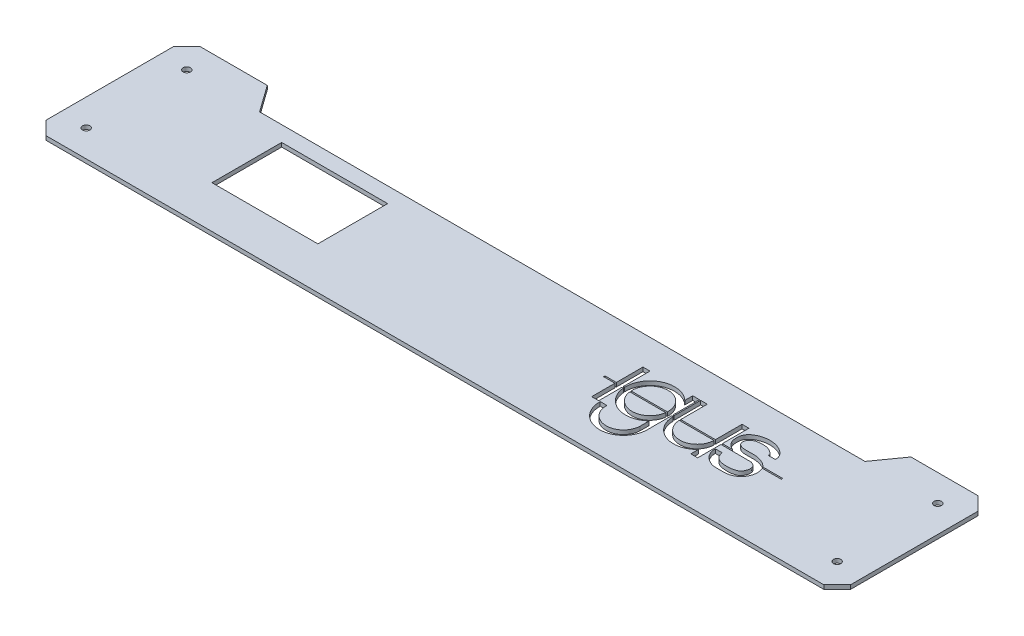
SolidWorks part; units mm, degrees
ref_plane "Front Plane" through (0, 0, 0) normal (0, 0, 1) x (1, 0, 0)
ref_plane "Top Plane" through (0, 0, 0) normal (0, 1, 0) x (1, 0, 0)
ref_plane "Right Plane" through (0, 0, 0) normal (1, 0, 0) x (0, 0, -1)
sketch "Sketch1" plane through (0, 0, 0) normal (0, 1, 0) x (1, 0, 0)
  line L0 (44.6193, 0) -> (44.6193, -115) construction
  line L1 (14.6193, 0) -> (64.6193, 0)
  line L2 (4.6193, -10) -> (4.6193, -105)
  line L3 (14.6193, -115) -> (64.6193, -115)
  line L4 (564.6193, 0) -> (564.6193, -115) construction
  line L6 (4.6193, -10) -> (14.6193, 0)
  line L7 (4.6193, -105) -> (14.6193, -115)
  line L9 (78.8949, -20) -> (530.3437, -20)
  line L10 (78.8949, -20) -> (64.6193, 0)
  line L11 (304.6193, 0) -> (304.6193, -115) construction
  line L12 (530.3437, -20) -> (544.6193, 0)
  line L13 (604.6193, -105) -> (594.6193, -115)
  line L14 (604.6193, -10) -> (594.6193, 0)
  line L16 (594.6193, -115) -> (544.6193, -115)
  line L17 (604.6193, -10) -> (604.6193, -105)
  line L18 (594.6193, 0) -> (544.6193, 0)
  line L19 (64.6193, -115) -> (544.6193, -115)
  circle A0 centre (24.6193, -20) radius 2.75
  circle A1 centre (24.6193, -95) radius 2.75
  circle A2 centre (584.6193, -95) radius 2.75
  circle A3 centre (584.6193, -20) radius 2.75
  point P0 (4.6193, 0)
  point P2 (4.6193, -115)
  point P28 (304.6193, -20)
  point P29 (304.6193, -95)
  point P34 (604.6193, -115)
  point P35 (604.6193, 0)
  dimension "D4" = 5.5
  dimension "D5" = 20
  dimension "D1" = 115
  dimension "D2" = 300
  dimension "D3" = 40
  dimension "D6" = 20
  dimension "D7" = 20
  dimension "D8" = 20
  dimension "D9" = 20
  dimension "D10" = 20
extrude "Boss-Extrude1" add sketch "Sketch1" along normal blind 3
sketch "Sketch2" plane through (0, 3, 0) normal (0, 1, 0) x (1, 0, 0)
  line L0 (393.0027, -80.0768) -> (398.0021, -80.0768)
  line L1 (386.6123, -41.8475) -> (391.8479, -41.8475)
  line L2 (386.6123, -41.8475) -> (386.6123, -61.6873)
  line L3 (386.6123, -80.0768) -> (391.8479, -80.0768)
  line L4 (391.8479, -41.8475) -> (391.8479, -61.6873)
  line L5 (423.7383, -47.7863) -> (423.7383, -41.8475)
  line L6 (466.527, -67.6702) -> (471.6598, -67.6702)
  line L7 (428.7377, -81.1843) -> (428.7377, -41.8475)
  line L8 (428.7377, -41.8475) -> (423.7383, -41.8475)
  line L9 (423.7383, -81.1843) -> (423.7383, -74.2978)
  line L10 (460.5247, -61.6873) -> (460.5247, -41.8475)
  line L11 (460.5247, -80.0768) -> (465.6606, -80.0768)
  line L12 (460.5247, -80.0768) -> (460.5247, -74.3998)
  line L13 (460.5247, -41.8475) -> (465.6606, -41.8475)
  line L14 (465.6606, -80.0768) -> (465.6606, -62.7545)
  line L15 (490.3889, -52.2144) -> (495.6647, -52.2144)
  line L16 (434.5855, -41.8475) -> (429.6272, -41.8475)
  line L17 (434.5855, -41.8475) -> (434.5855, -61.6873)
  line L18 (434.5855, -61.6873) -> (460.5247, -61.6873)
  line L19 (429.6272, -41.8475) -> (429.6272, -61.6873)
  line L20 (386.6123, -62.7545) -> (386.6123, -80.0768)
  line L21 (378.213, -61.6873) -> (386.6123, -61.6873)
  line L22 (378.213, -61.6873) -> (378.213, -62.7545)
  line L23 (378.213, -62.7545) -> (386.6123, -62.7545)
  line L24 (510.6818, -61.6873) -> (510.6818, -62.7545)
  line L25 (391.8479, -61.6873) -> (392.8262, -61.6873)
  line L26 (391.8479, -62.7545) -> (392.8952, -62.7545)
  line L27 (391.8479, -62.7545) -> (391.8479, -80.0768)
  line L28 (397.6051, -61.6873) -> (424.6303, -61.6873)
  line L29 (397.6985, -62.7545) -> (424.5369, -62.7545)
  line L30 (428.7377, -61.6873) -> (429.6272, -61.6873)
  line L31 (428.7377, -62.7545) -> (429.8284, -62.7545)
  line L32 (434.5861, -62.7545) -> (460.5173, -62.7545)
  line L33 (495.7621, -61.6873) -> (510.6818, -61.6873)
  line L34 (496.4657, -62.7545) -> (510.6818, -62.7545)
  line L35 (465.6606, -61.6873) -> (465.6606, -41.8475)
  line L36 (488.4179, -62.8551) -> (465.6606, -62.7545)
  line L37 (473.3823, -61.6873) -> (465.6606, -61.6873)
  line L38 (85.7343, -57.7545) -> (-190.1452, -57.7545) construction
  line L40 (274.9754, -57.7545) -> (550.8548, -57.7545) construction
  circle A0 centre (389.0819, -35.7229) radius 2.5185
  arc A1 (397.6985, -62.7545) -> (424.5369, -62.7545) centre (411.1177, -61.0421) ccw
  arc A2 (423.7383, -47.7863) -> (392.8262, -61.6873) centre (411.1177, -61.0421) ccw
  arc A3 (398.0021, -80.0768) -> (423.7383, -81.1843) centre (410.8702, -80.6306) ccw
  arc A4 (428.7377, -81.1843) -> (393.0027, -80.0768) centre (410.8702, -80.6306) cw
  arc A5 (434.5861, -62.7545) -> (460.5173, -62.7545) centre (447.5517, -62.3164) ccw
  arc A6 (429.8284, -62.7545) -> (460.5247, -74.3998) centre (447.5517, -62.3164) ccw
  arc A7 (392.8952, -62.7545) -> (423.7383, -74.2978) centre (411.1177, -61.0421) ccw
  arc A8 (424.6303, -61.6873) -> (397.6051, -61.6873) centre (411.1177, -61.0421) ccw
  spline S0 degree 3 poles (495.6647, -52.2144) (495.9196, -48.4128) (490.4372, -42.9313) (480.7994, -41.2133) (473.0043, -43.1242) (467.5156, -47.6539) (467.0249, -52.6397) (467.8049, -58.0953) (470.9593, -60.8159) (473.3823, -61.6873) knots 0 0 0 0 0.214336 0.39323 0.565847 0.67611 0.787927 0.84268 1 1 1 1
  spline S1 degree 3 poles (490.3889, -52.2144) (490.6662, -51.3584) (489.7905, -50.0224) (487.9321, -48.8431) (485.5465, -47.5103) (482.5623, -47.0434) (479.1347, -47.159) (476.0682, -47.6148) (473.4883, -49.3776) (472.0481, -51.653) (471.9846, -54.1678) (473.4783, -55.9924) (477.4706, -57.607) (483.3638, -56.5604) (489.7413, -57.626) (493.7251, -59.5318) (495.3022, -61.0952) (495.7621, -61.6873) knots 0 0 0 0 0.023974 0.0429 0.065707 0.104505 0.130316 0.168034 0.194386 0.220522 0.245719 0.2628 0.28726 0.369622 0.434467 0.476788 0.498808 0.498808 0.498808 0.498808
  spline S2 degree 3 poles (471.6598, -67.6702) (471.4673, -68.6463) (472.08, -69.7871) (472.7507, -71.3283) (473.6708, -72.1427) (474.7315, -73.1784) (476.2668, -73.9655) (478.3059, -74.5124) (480.6367, -74.7056) (483.2812, -74.7698) (485.8899, -74.5277) (488.2114, -73.7335) (490.4552, -72.7194) (491.5262, -70.5904) (492.3705, -68.547) (492.2726, -66.5441) (491.5727, -64.0149) (489.3739, -63.4112) (488.4179, -62.8551) knots 0 0 0 0 0.081184 0.107905 0.143901 0.185104 0.235866 0.290216 0.366526 0.436729 0.518739 0.590002 0.64943 0.723575 0.786666 0.838093 0.894822 1 1 1 1
  spline S3 degree 3 poles (496.4657, -62.7545) (496.557, -62.9208) (497.1548, -64.1138) (497.6759, -66.848) (497.3119, -70.7801) (495.5754, -74.302) (492.9872, -77.0987) (489.9409, -78.7717) (486.6945, -79.5092) (483.0537, -79.6843) (479.2036, -79.7437) (475.3935, -79.3672) (472.3901, -77.7238) (469.577, -76) (467.1901, -72.426) (466.2475, -69.5869) (466.527, -67.6702) knots 0.51138 0.51138 0.51138 0.51138 0.516991 0.550898 0.592187 0.632311 0.665074 0.704087 0.733344 0.763284 0.81203 0.848329 0.874619 0.912981 0.944693 1 1 1 1
extrude "Cut-Extrude1" cut sketch "Sketch2" against normal blind 494 contours L26 A7 L9 A3 L0 A4 L7 L8 L5 A2 L25 L4 L1 L2 L21 L22 L23 L20 L3 L27 A8 L28 A1 L29 | S3 L34 L24 L33 S1 L15 S0 L37 L35 L13 L10 L18 L17 L16 L19 L30 L7 L31 A6 L12 L11 L14 L36 S2 L6 A5 L32 region at (395.5024, 3, 80.836) region at (466.3965, 3, 62.4002)
sketch "Sketch3" plane through (0, 3, 0) normal (0, 1, 0) x (1, 0, 0)
  line L0 (4.6193, -57.5) -> (343.7959, -57.5) construction
  line L1 (4.6193, -10) -> (4.6193, -105) construction
  line L3 (106.8607, -83.5) -> (185.8607, -83.5)
  line L4 (106.8607, -83.5) -> (106.8607, -31.5)
  line L5 (106.8607, -31.5) -> (185.8607, -31.5)
  line L6 (185.8607, -83.5) -> (185.8607, -31.5)
  line L7 (106.8607, -83.5) -> (185.8607, -31.5) construction
  line L8 (106.8607, -31.5) -> (185.8607, -83.5) construction
  point P4 (146.3607, -57.5)
  dimension "D1" = 79
  dimension "D2" = 52
extrude "Cut-Extrude2" cut sketch "Sketch3" against normal blind 10
